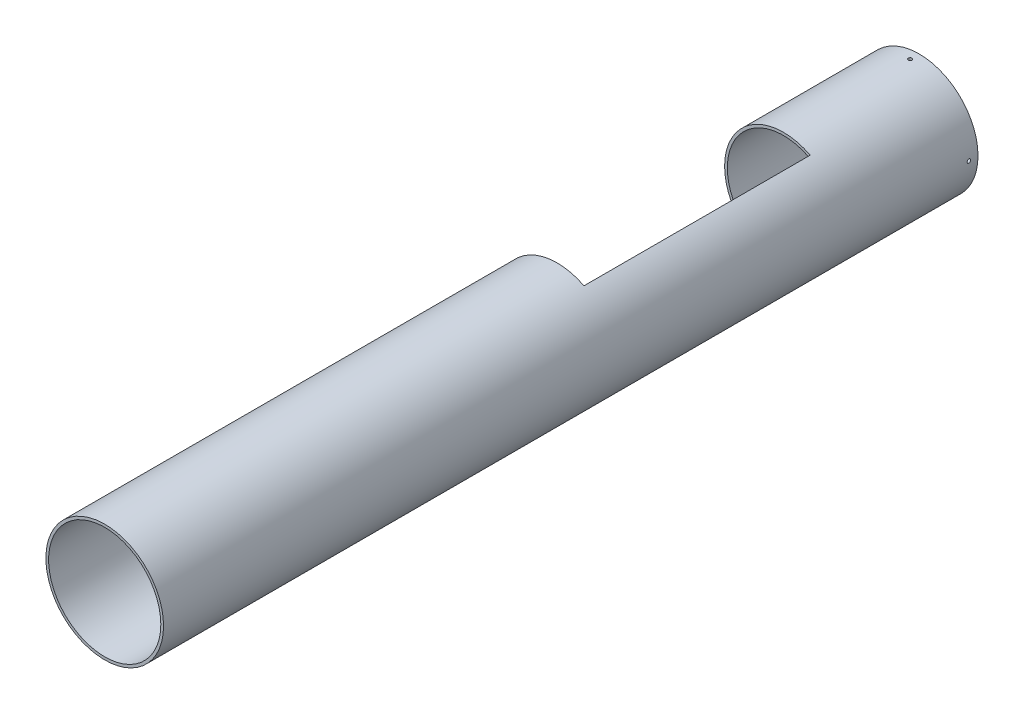
SolidWorks part; units mm, degrees
ref_plane "Front Plane" through (0, 0, 0) normal (0, 0, 1) x (1, 0, 0)
ref_plane "Top Plane" through (0, 0, 0) normal (0, 1, 0) x (1, 0, 0)
ref_plane "Right Plane" through (0, 0, 0) normal (1, 0, 0) x (0, 0, -1)
sketch "Sketch1" plane through (0, 0, 0) normal (0, 0, 1) x (1, 0, 0)
  circle A0 centre (0, 0) radius 62
  circle A1 centre (0, 0) radius 65
  dimension "D1" = 124
  dimension "D2" = 3
extrude "Boss-Extrude1" add sketch "Sketch1" along normal blind 900
sketch "Sketch2" plane through (0, 0, 0) normal (0, 1, 0) x (1, 0, 0)
  line L0 (62, 0) -> (-62, 0) construction
  circle A0 centre (0, -224) radius 1
  circle A1 centre (0, -264) radius 1
  dimension "D1" = 2
  dimension "D3" = 2
  dimension "D2" = 224
  dimension "D4" = 40
ref_plane "Plane1" through (0, 0, 0) normal (-0.7071, 0.7071, 0) x (0.7071, 0.7071, 0)
ref_plane "Plane2" through (-14.1421, 14.1421, 0) normal (-0.7071, 0.7071, 0) x (0.7071, 0.7071, 0)
sketch "Sketch4" plane through (-14.1421, 14.1421, 0) normal (-0.7071, 0.7071, 0) x (0.7071, 0.7071, 0)
  line L0 (-65, 0) -> (-65, -900) construction
  line L1 (-65, -150) -> (65, -150)
  line L2 (-65, -150) -> (-65, -400)
  line L3 (-65, -400) -> (65, -400)
  line L4 (65, -150) -> (65, -400)
  line L5 (65, -900) -> (65, 0) construction
  line L6 (65, 0) -> (-65, 0) construction
  dimension "D1" = 150
  dimension "D2" = 250
extrude "Cut-Extrude4" cut sketch "Sketch4" along normal blind 516
sketch "Sketch5" plane through (0, 0, 0) normal (0, 1, 0) x (1, 0, 0)
  line L0 (-62, 0) -> (62, 0) construction
  circle A0 centre (0, -10) radius 2
  dimension "D1" = 4
  dimension "D2" = 10
extrude "Cut-Extrude5" cut sketch "Sketch5" against normal blind 85
pattern_circular "CirPattern1" count 4 every 90 about axis through (0, 0, 900) along (0, 0, -1) of "Cut-Extrude5"
